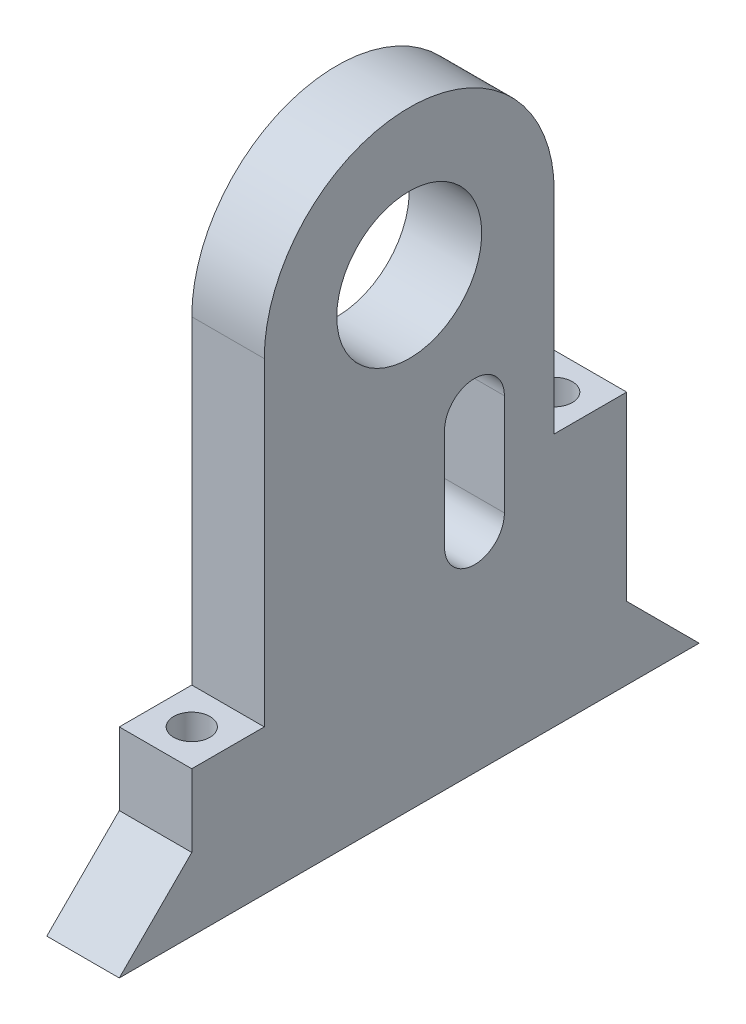
SolidWorks part; units mm, degrees
ref_plane "Front Plane" through (0, 0, 0) normal (0, 0, 1) x (1, 0, 0)
ref_plane "Top Plane" through (0, 0, 0) normal (0, 1, 0) x (1, 0, 0)
ref_plane "Right Plane" through (0, 0, 0) normal (1, 0, 0) x (0, 0, -1)
sketch "Sketch1" plane through (0, 0, 0) normal (1, 0, 0) x (0, 0, -1)
  line L0 (10, 0) -> (-10, 0)
  line L1 (-10, 10) -> (-10, 32)
  line L2 (0, 42) -> (0, 0) construction
  line L3 (20, 0) -> (10, 0)
  line L4 (10, 17.5) -> (10, 32)
  line L5 (15, 10) -> (15, 5)
  line L6 (-15, 5) -> (-20, 0)
  line L7 (-15, 10) -> (-15, 5)
  line L8 (-20, 0) -> (-10, 0)
  line L10 (15, 5) -> (20, 0)
  line L11 (-15, 10) -> (-10, 10)
  line L12 (15, 10) -> (15, 17.5)
  line L13 (15, 17.5) -> (10, 17.5)
  arc A0 (-10, 32) -> (10, 32) centre (0, 32) cw
  dimension "D1" = 10
extrude "Boss-Extrude1" add sketch "Sketch1" along normal blind 5 contours A0 L4 L13 L12 L5 L10 L3 L0 L8 L6 L7 L11 L1
sketch "Sketch3" plane through (0, 0, 0) normal (-1, 0, 0) x (0, 0, 1)
  line L0 (-10, 32) -> (10, 32) construction
  line L1 (0, 32) -> (0, 0) construction
hole_wizard "Ø10.0mm Dowel Hole1" positions "3DSketch2" profile "Sketch4" hole size "Ø10.0" standard "ISO"
sketch3d "3DSketch2"
  point P0 (0, 32, 0)
sketch "Sketch4" plane through (0, 32, 0) normal (0, 1, 0) x (0, 0, 1)
  line L0 (0, 0) -> (0, 28.0043)
  line L1 (0, 28.0043) -> (5, 25)
  line L2 (5, 25) -> (5, 0)
  line L5 (5, 0) -> (0, 0)
  line L10 (0, 28.0043) -> (-5, 25) construction
  line L11 (0, -6.35) -> (0, 107.95) construction
  dimension "Hole Dia." = 10
  dimension "Hole Depth" = 25
  dimension "Drill Angle" = 118
sketch "Sketch5" plane through (5, 0, 0) normal (1, 0, 0) x (0, 0, -1)
  line L0 (0, 32) -> (10, 32) construction
  line L1 (10, 32) -> (-10, 32) construction
  line L2 (20, 0) -> (-20, 0) construction
  line L5 (4.5, 21.5) -> (4.5, 14.5) construction
  line L6 (6.5636, 21.5) -> (6.5636, 14.5)
  line L7 (2.4364, 21.5) -> (2.4364, 14.5)
  arc A0 (6.5636, 21.5) -> (2.4364, 21.5) centre (4.5, 21.5) ccw
  arc A1 (2.4364, 14.5) -> (6.5636, 14.5) centre (4.5, 14.5) ccw
  point P9 (4.5, 18)
  dimension "D1" = 18
extrude "Cut-Extrude1" cut sketch "Sketch5" against normal blind 10
sketch "Sketch6" plane through (0, 0, 0) normal (0, -1, 0) x (-1, 0, 0)
  line L0 (-2.5, -10) -> (-2.5, 10) construction
  line L1 (-5, -10) -> (0, -10) construction
  line L2 (-5, 10) -> (0, 10) construction
sketch "Sketch7" plane through (0, 0, 0) normal (0, -1, 0) x (-1, 0, 0)
  line L0 (0, 0) -> (-5, 0) construction
  line L1 (-5, 20) -> (-5, -20) construction
  line L2 (-2.5, 0) -> (-2.5, 5) construction
  line L3 (-2.5, 0) -> (-2.5, -5) construction
  dimension "D1" = 5
  dimension "D2" = 5
sketch "Sketch8" plane through (0, 10, 0) normal (0, 1, 0) x (1, 0, 0)
  line L0 (2.5, 10) -> (2.5, 15) construction
  line L1 (5, 10) -> (0, 10) construction
  line L2 (5, 15) -> (0, 15) construction
  line L3 (2.5, 12.5) -> (0, 12.5) construction
  line L4 (0, 15) -> (0, 10) construction
  line L5 (2.5, -15) -> (2.5, -10) construction
  line L6 (5, -15) -> (0, -15) construction
  line L7 (5, -10) -> (0, -10) construction
  line L8 (2.5, -12.5) -> (0, -12.5) construction
  line L9 (0, -15) -> (0, -10) construction
hole_wizard "M3 Tapped Hole1" positions "Sketch10" profile "Sketch9" tap size "M3" standard "ISO"
sketch "Sketch10" plane through (0, 10, 0) normal (0, 1, 0) x (1, 0, 0)
  point P0 (2.5, -12.5)
  point P3 (2.5, 12.5)
sketch "Sketch9" plane through (2.5, 10, 12.5) normal (1, 0, 0) x (0, 0, 1)
  line L0 (0, 0) -> (0, 18.2511)
  line L1 (0, 18.2511) -> (1.25, 17.5)
  line L2 (1.25, 17.5) -> (1.25, 0)
  line L5 (1.25, 0) -> (0, 0)
  line L10 (0, 18.2511) -> (-1.25, 17.5) construction
  line L11 (0, -6.35) -> (0, 107.95) construction
  dimension "Tap Drill Dia." = 2.5
  dimension "Tap Drill Depth" = 17.5
  dimension "Drill Angle" = 118
sketch "Sketch11" plane through (0, 17.5, 0) normal (0, 1, 0) x (1, 0, 0)
  line L0 (0, 10) -> (0, 12.5) construction
  line L1 (0, 15) -> (0, 10) construction
  line L2 (0, 12.5) -> (5, 12.5) construction
  line L3 (5, 15) -> (5, 10) construction
  line L4 (5, 12.5) -> (2.5, 12.5) construction
hole_wizard "M3 Tapped Hole2" positions "Sketch13" profile "Sketch12" tap size "M3" standard "ISO"
sketch "Sketch13" plane through (0, 17.5, 0) normal (0, 1, 0) x (1, 0, 0)
  point P0 (2.5, 12.5)
sketch "Sketch12" plane through (2.5, 17.5, -12.5) normal (1, 0, 0) x (0, 0, 1)
  line L0 (0, 0) -> (0, 18.2511)
  line L1 (0, 18.2511) -> (1.25, 17.5)
  line L2 (1.25, 17.5) -> (1.25, 0)
  line L5 (1.25, 0) -> (0, 0)
  line L10 (0, 18.2511) -> (-1.25, 17.5) construction
  line L11 (0, -6.35) -> (0, 107.95) construction
  dimension "Tap Drill Dia." = 2.5
  dimension "Tap Drill Depth" = 17.5
  dimension "Drill Angle" = 118
